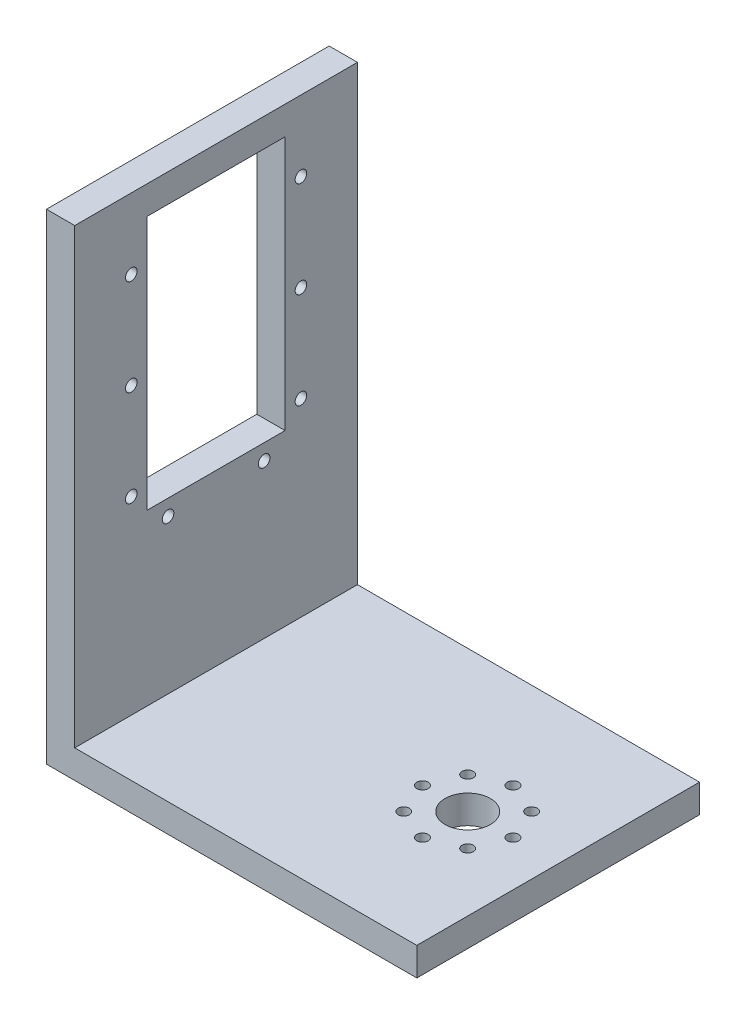
SolidWorks part; units mm, degrees
ref_plane "Front Plane" through (0, 0, 0) normal (0, 0, 1) x (1, 0, 0)
ref_plane "Top Plane" through (0, 0, 0) normal (0, 1, 0) x (1, 0, 0)
ref_plane "Right Plane" through (0, 0, 0) normal (1, 0, 0) x (0, 0, -1)
sketch "Sketch1" plane through (0, 0, 0) normal (0, 1, 0) x (1, 0, 0)
  line L0 (65.5, 25) -> (49.5, 25) construction
  line L1 (0, 0) -> (65.5, 0)
  line L2 (0, 0) -> (0, 50)
  line L3 (0, 50) -> (65.5, 50)
  line L4 (65.5, 0) -> (65.5, 50)
  line L5 (49.5, 33) -> (49.5, 25) construction
  circle A0 centre (49.5, 25) radius 4
  circle A1 centre (49.5, 33) radius 1
  circle A2 centre (55.1569, 30.6569) radius 1
  circle A3 centre (57.5, 25) radius 1
  circle A4 centre (55.1569, 19.3431) radius 1
  circle A5 centre (49.5, 17) radius 1
  circle A6 centre (43.8431, 19.3431) radius 1
  circle A7 centre (41.5, 25) radius 1
  circle A8 centre (43.8431, 30.6569) radius 1
  point P11 (0, 0)
  point P12 (0, 0)
  point P26 (49.5, 25)
  dimension "D3" = 8
  dimension "D5" = 2
  dimension "D1" = 65.5
  dimension "D2" = 50
  dimension "D4" = 16
  dimension "D7" = 8
  dimension "D6" = 8
extrude "Boss-Extrude1" add sketch "Sketch1" along normal blind 5
sketch "Sketch3" plane through (0, 0, 0) normal (0, 1, 0) x (1, 0, 0)
  line L0 (65.5, 50) -> (0, 50) construction
  line L1 (0, 0) -> (5, 0)
  line L2 (0, 0) -> (0, 50)
  line L3 (0, 50) -> (5, 50)
  line L4 (5, 0) -> (5, 50)
  dimension "D1" = 5
extrude "Boss-Extrude2" add sketch "Sketch3" along normal blind 85
sketch "Sketch4" plane through (0, 0, 0) normal (-1, 0, 0) x (0, 0, 1)
  line L0 (-25, 85) -> (-25, 23.7384) construction
  line L1 (-50, 85) -> (0, 85) construction
  line L2 (-40, 72.5) -> (-10, 72.5) construction
  line L3 (-37.2, 35) -> (-12.8, 35)
  line L4 (-37.2, 35) -> (-37.2, 80)
  line L5 (-37.2, 80) -> (-12.8, 80)
  line L6 (-12.8, 35) -> (-12.8, 80)
  line L7 (-40, 55.5) -> (-10, 55.5) construction
  line L9 (-40, 38.5) -> (-33.5, 32.2) construction
  line L10 (-40, 55.5) -> (-40, 38.5) construction
  circle A0 centre (-40, 72.5) radius 1.025
  circle A1 centre (-10, 72.5) radius 1.025
  circle A2 centre (-40, 55.5) radius 1.025
  circle A3 centre (-40, 38.5) radius 1.025
  circle A5 centre (-10, 55.5) radius 1.025
  circle A6 centre (-33.5, 32.2) radius 1.025
  circle A8 centre (-16.5, 32.2) radius 1.025
  circle A9 centre (-10, 38.5) radius 1.025
  point P8 (-25, 80)
  point P9 (-25, 80)
  point P12 (-25, 72.5)
  dimension "D4" = 2.05
  dimension "D1" = 24.4
  dimension "D2" = 45
  dimension "D3" = 30
  dimension "D5" = 17
  dimension "D6" = 7.5
  dimension "D7" = 17
  dimension "D8" = 6.5
  dimension "D9" = 6.3
  dimension "D10" = 5
extrude "Cut-Extrude1" cut sketch "Sketch4" against normal through all
